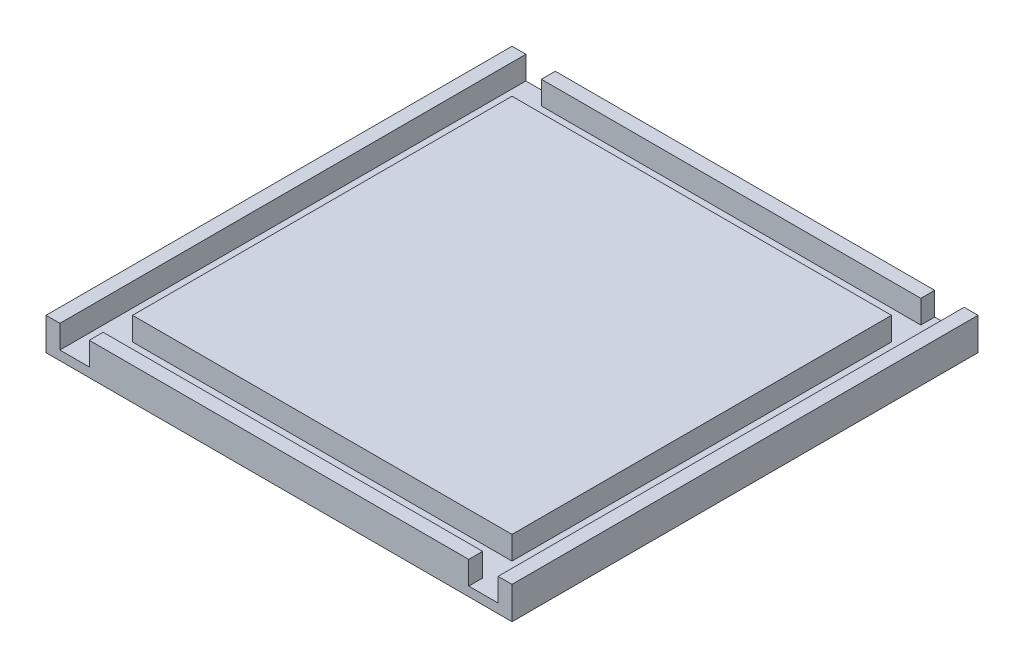
SolidWorks part; units mm, degrees
ref_plane "Front Plane" through (0, 0, 0) normal (0, 0, 1) x (1, 0, 0)
ref_plane "Top Plane" through (0, 0, 0) normal (0, 1, 0) x (1, 0, 0)
ref_plane "Right Plane" through (0, 0, 0) normal (1, 0, 0) x (0, 0, -1)
sketch "Sketch1" plane through (0, 0, 0) normal (0, 1, 0) x (1, 0, 0)
  line L0 (0, 82) -> (0, 88.35) construction
  line L1 (0, 0) -> (82, 0)
  line L2 (0, 0) -> (0, 82)
  line L3 (0, 82) -> (82, 82)
  line L4 (82, 0) -> (82, 82)
  line L5 (-6.35, 88.35) -> (88.35, 88.35)
  line L6 (-6.35, 88.35) -> (-6.35, -6.35)
  line L7 (-6.35, -6.35) -> (88.35, -6.35)
  line L8 (88.35, 88.35) -> (88.35, -6.35)
  line L9 (91.35, -9.35) -> (-9.35, -9.35)
  line L10 (91.35, -9.35) -> (91.35, 91.35)
  line L11 (91.35, 91.35) -> (-9.35, 91.35)
  line L12 (-9.35, -9.35) -> (-9.35, 91.35)
  line L13 (0, 82) -> (-6.35, 82) construction
  line L14 (-6.35, 88.35) -> (-6.35, 91.35) construction
  line L15 (-6.35, 88.35) -> (-9.35, 88.35) construction
  line L16 (82, 0) -> (88.35, 0) construction
  line L17 (82, 0) -> (82, -6.35) construction
  line L18 (88.35, -6.35) -> (88.35, -9.35) construction
  line L19 (88.35, -6.35) -> (91.35, -6.35) construction
  dimension "D1" = 82
  dimension "D2" = 3
  dimension "D3" = 6.35
extrude "Boss-Extrude1" add sketch "Sketch1" along normal blind 5 contours L12 L9 L10 L11 L5 L8 L7 L6 | L1 L4 L3 L2 region at (41, 0, -41) region at (41, 0, 7.9259)
sketch "Sketch2" plane through (0, 0, 0) normal (0, -1, 0) x (1, 0, 0)
  line L1 (-9.35, 9.35) -> (91.35, 9.35)
  line L2 (-9.35, 9.35) -> (-9.35, -91.35)
  line L3 (-9.35, -91.35) -> (91.35, -91.35)
  line L4 (91.35, 9.35) -> (91.35, -91.35)
extrude "Boss-Extrude2" add sketch "Sketch2" along normal blind 2
sketch "Sketch3" plane through (0, 0, 0) normal (0, 1, 0) x (1, 0, 0)
  line L0 (82, 0) -> (82, 82) construction
  line L1 (88.35, 91.35) -> (82, 91.35)
  line L2 (88.35, 91.35) -> (88.35, -9.35)
  line L3 (88.35, -9.35) -> (82, -9.35)
  line L4 (82, 91.35) -> (82, -9.35)
  line L5 (88.35, 88.35) -> (88.35, -6.35) construction
  line L6 (91.35, 91.35) -> (-9.35, 91.35) construction
  line L7 (91.35, -9.35) -> (-9.35, -9.35) construction
  line L8 (41, 82) -> (41, 0) construction
  line L9 (0, 82) -> (82, 82) construction
  line L10 (0, 0) -> (82, 0) construction
  line L11 (-6.35, -9.35) -> (0, -9.35)
  line L12 (0, 91.35) -> (0, -9.35)
  line L13 (-6.35, 91.35) -> (0, 91.35)
  line L14 (-6.35, 91.35) -> (-6.35, -9.35)
extrude "Cut-Extrude1" cut sketch "Sketch3" along normal up to surface (5 mm away) up to face at (41, 5, -41)
